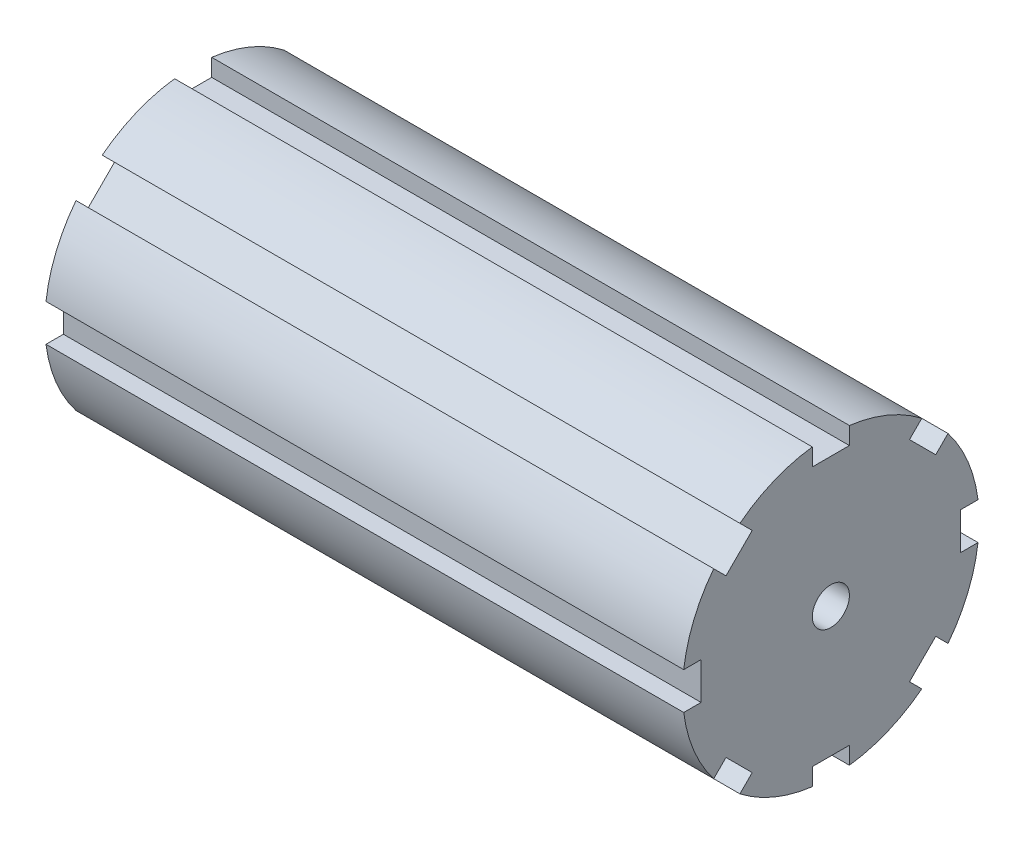
SolidWorks part; units mm, degrees
ref_plane "Front Plane" through (0, 0, 0) normal (0, 0, 1) x (1, 0, 0)
ref_plane "Top Plane" through (0, 0, 0) normal (0, 1, 0) x (1, 0, 0)
ref_plane "Right Plane" through (0, 0, 0) normal (1, 0, 0) x (0, 0, -1)
sketch "Sketch1" plane through (0, 0, 0) normal (1, 0, 0) x (0, 0, -1)
  circle A0 centre (0, 0) radius 25.4
  dimension "D1" = 50.8
extrude "Boss-Extrude1" add sketch "Sketch1" against normal blind 109.22 contours A0
sketch "Sketch2" plane through (0, 0, 0) normal (1, 0, 0) x (0, 0, -1)
  line L0 (22.4506, 17.9605) -> (17.9605, 22.4506)
  line L1 (3.175, 22.225) -> (-3.175, 22.225)
  line L2 (3.175, 22.225) -> (3.175, 28.575)
  line L3 (3.175, 28.575) -> (-3.175, 28.575)
  line L4 (-3.175, 22.225) -> (-3.175, 28.575)
  line L5 (3.175, 22.225) -> (-3.175, 28.575) construction
  line L6 (3.175, 28.575) -> (-3.175, 22.225) construction
  line L7 (13.4704, 17.9605) -> (17.9605, 22.4506)
  line L8 (17.9605, 13.4704) -> (22.4506, 17.9605)
  line L9 (17.9605, 13.4704) -> (13.4704, 17.9605)
  line L10 (28.575, -3.175) -> (28.575, 3.175)
  line L11 (22.225, 3.175) -> (28.575, 3.175)
  line L12 (22.225, -3.175) -> (28.575, -3.175)
  line L13 (22.225, -3.175) -> (22.225, 3.175)
  line L14 (17.9605, -22.4506) -> (22.4506, -17.9605)
  line L15 (17.9605, -13.4704) -> (22.4506, -17.9605)
  line L16 (13.4704, -17.9605) -> (17.9605, -22.4506)
  line L17 (13.4704, -17.9605) -> (17.9605, -13.4704)
  line L18 (-3.175, -28.575) -> (3.175, -28.575)
  line L19 (3.175, -22.225) -> (3.175, -28.575)
  line L20 (-3.175, -22.225) -> (-3.175, -28.575)
  line L21 (-3.175, -22.225) -> (3.175, -22.225)
  line L22 (-22.4506, -17.9605) -> (-17.9605, -22.4506)
  line L23 (-13.4704, -17.9605) -> (-17.9605, -22.4506)
  line L24 (-17.9605, -13.4704) -> (-22.4506, -17.9605)
  line L25 (-17.9605, -13.4704) -> (-13.4704, -17.9605)
  line L26 (-28.575, 3.175) -> (-28.575, -3.175)
  line L27 (-22.225, -3.175) -> (-28.575, -3.175)
  line L28 (-22.225, 3.175) -> (-28.575, 3.175)
  line L29 (-22.225, 3.175) -> (-22.225, -3.175)
  line L30 (-17.9605, 22.4506) -> (-22.4506, 17.9605)
  line L31 (-17.9605, 13.4704) -> (-22.4506, 17.9605)
  line L32 (-13.4704, 17.9605) -> (-17.9605, 22.4506)
  line L33 (-13.4704, 17.9605) -> (-17.9605, 13.4704)
  circle A0 centre (0, 0) radius 25.4 construction
  circle A1 centre (0, 0) radius 3.175
  point P0 (0, 25.4)
  point P38 (0, 0)
  dimension "D4" = 6.35
  dimension "D1" = 6.35
  dimension "D2" = 6.35
  dimension "D3" = 8
extrude "Cut-Extrude1" cut sketch "Sketch2" against normal blind 109.22
